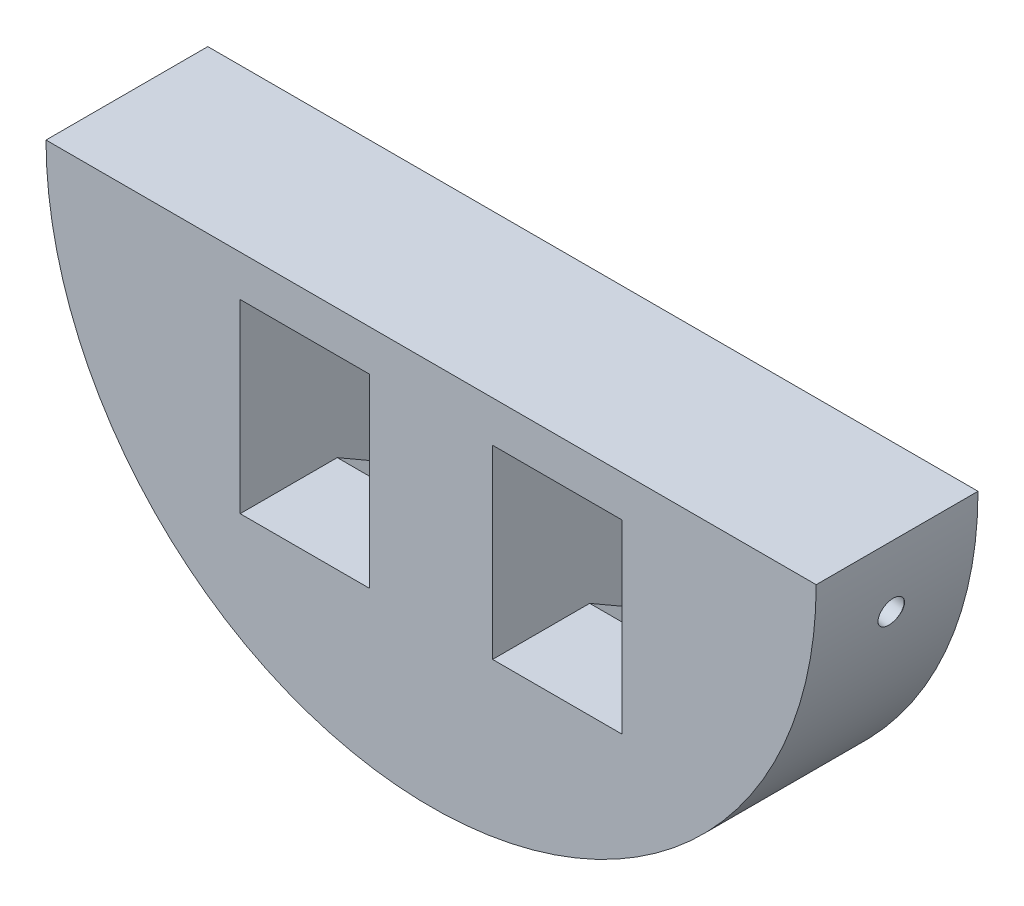
SolidWorks part; units mm, degrees
ref_plane "Front Plane" through (0, 0, 0) normal (0, 0, 1) x (1, 0, 0)
ref_plane "Top Plane" through (0, 0, 0) normal (0, 1, 0) x (1, 0, 0)
ref_plane "Right Plane" through (0, 0, 0) normal (1, 0, 0) x (0, 0, -1)
sketch "Sketch1" plane through (0, 0, 0) normal (0, 0, 1) x (1, 0, 0)
  line L0 (-119, 0) -> (0, 0)
  line L3 (-50, -35) -> (-30, -35)
  line L4 (-50, -35) -> (-50, -15)
  line L5 (-50, -15) -> (-30, -15)
  line L6 (-30, -35) -> (-30, -15)
  line L7 (-89, -35) -> (-69, -35)
  line L8 (-89, -35) -> (-89, -15)
  line L9 (-89, -15) -> (-69, -15)
  line L10 (-69, -35) -> (-69, -15)
  arc A1 (-119, 0) -> (0, 0) centre (-59.5, 0) ccw
  dimension "D1" = 30
  dimension "D7" = 59.5
  dimension "D2" = 15
  dimension "D3" = 30
  dimension "D4" = 20
extrude "Boss-Extrude1" add sketch "Sketch1" along normal blind 25
hole_wizard "Ø4.0mm Dowel Hole2" positions "3DSketch2" profile "Sketch4" hole size "Ø4.0" standard "ANSI Metric"
sketch3d "3DSketch2"
  line L2 (0, 0, 25) -> (0, 0, 0) construction
  line L4 (0, 0, 25) -> (0, 0, 0) construction
  line L5 (0, 0, 12.5) -> (-0.9039, -10.3321, 12.5) construction
  line L8 (-59.5, 0, 0) -> (-59.5, 0, 25) construction
  line L9 (0, 0, 0) -> (-119, 0, 0) construction
  line L10 (0, 0, 25) -> (-119, 0, 25) construction
  line L12 (-59.5, 0, 12.5) -> (-0.9039, -10.3321, 12.5) construction
  line L16 (-59.5, 0, 12.5) -> (0, 0, 12.5) construction
  point P0 (-0.9039, -10.3321, 12.5)
  point P16 (-0.9039, -10.3321, 12.5)
  point P23 (-0.9039, -10.3321, 12.5)
  point P25 (-0.9039, -10.3321, 12.5)
  dimension "D1" = 10
sketch "Sketch4" plane through (-0.9039, -10.3321, 12.5) normal (0, 0, 1) x (0.1736, 0.9848, 0)
  line L0 (0, 0) -> (0, 11.2017)
  line L1 (0, 11.2017) -> (2, 10)
  line L2 (2, 10) -> (2, 0.025)
  line L3 (2, 0.025) -> (2.025, 0)
  line L5 (2.025, 0) -> (0, 0)
  line L6 (-2, 0.025) -> (-2.025, 0) construction
  line L10 (0, 11.2017) -> (-2, 10) construction
  line L11 (0, -6.35) -> (0, 107.95) construction
  dimension "Hole Dia." = 4
  dimension "Hole Depth" = 10
  dimension "Near C'Sink Dia." = 4.05
  dimension "Near C'Sink Angle" = 90
  dimension "Drill Angle" = 118
pattern_circular "CirPattern1" count 5 over 160 about axis through (-59.5, 0, 0) along (0, 0, 1) of "Ø4.0mm Dowel Hole2" reverse direction yes
chamfer "Chamfer1" distance 15 angle 30 2 edges at (-79, -15, 25) (-40, -15, 25) first distance on face at (-79, -15, 12.5) first distance on face at (-40, -15, 12.5)
chamfer "Chamfer2" distance 10 angle 30 2 edges at (-40, -35, 0) (-79, -35, 0) first distance on face at (-40, -35, 12.5) first distance on face at (-79, -35, 12.5)
